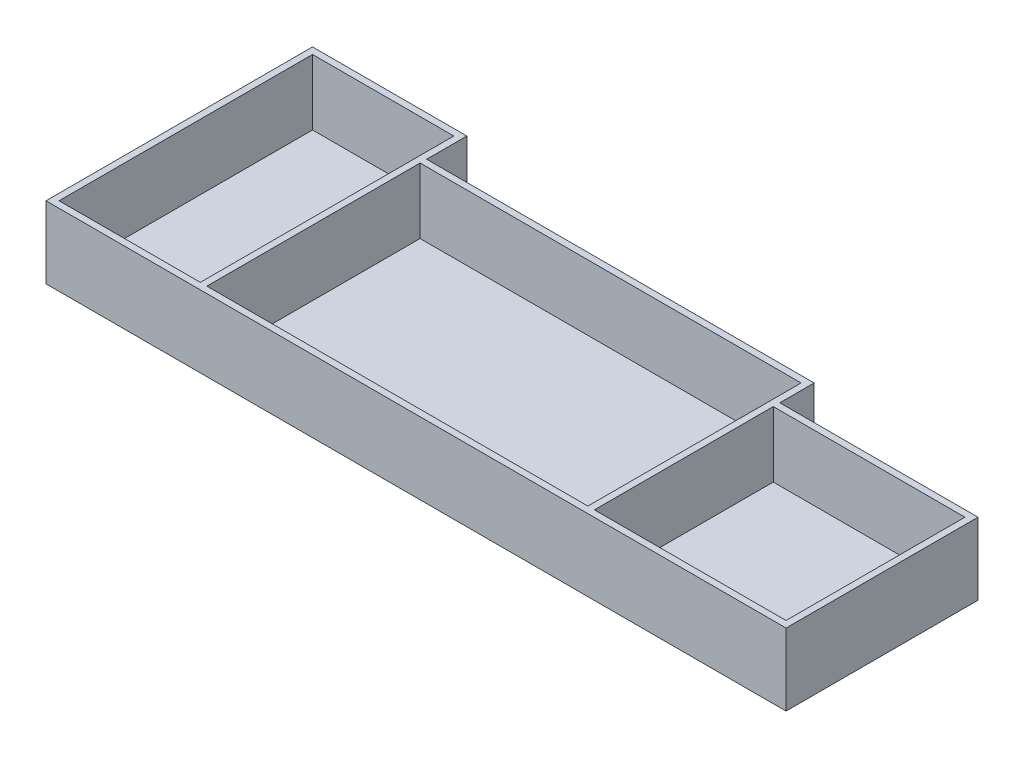
SolidWorks part; units mm, degrees
ref_plane "Front Plane" through (0, 0, 0) normal (0, 0, 1) x (1, 0, 0)
ref_plane "Top Plane" through (0, 0, 0) normal (0, 1, 0) x (1, 0, 0)
ref_plane "Right Plane" through (0, 0, 0) normal (1, 0, 0) x (0, 0, -1)
sketch "Sketch1" plane through (0, 0, 0) normal (0, 1, 0) x (1, 0, 0)
  line L0 (2, 79.5) -> (45.2, 79.5)
  line L1 (0, 0) -> (2, 0)
  line L2 (0, 0) -> (0, 2)
  line L6 (0, 2) -> (0, 79.5)
  line L8 (2, 2) -> (2, 79.5)
  line L10 (0, 79.5) -> (0, 81.5)
  line L11 (0, 81.5) -> (2, 81.5)
  line L13 (2, 2) -> (45.2, 2)
  line L15 (2, 0) -> (44.2, 0)
  line L17 (44.2, 0) -> (46.2, 0)
  line L21 (47.2, 2) -> (163.7, 2)
  line L23 (46.2, 0) -> (162.7, 0)
  line L27 (162.7, 0) -> (164.7, 0)
  line L29 (165.7, 2) -> (224.3, 2)
  line L31 (164.7, 0) -> (224.3, 0)
  line L34 (224.3, 2) -> (224.3, 0)
  line L35 (224.3, 0) -> (226.3, 0)
  line L36 (226.3, -4.0599) -> (226.3, 0)
  line L38 (45.2, 2) -> (45.2, 66.2)
  line L40 (47.2, 2) -> (47.2, 67.2)
  line L44 (45.2, 66.2) -> (45.2, 68.2)
  line L46 (163.7, 2) -> (163.7, 53.7)
  line L48 (165.7, 2) -> (165.7, 56.7)
  line L52 (163.7, 53.7) -> (163.7, 55.7)
  line L53 (45.2, 79.5) -> (45.2, 68.2)
  line L54 (2, 81.5) -> (47.2, 81.5)
  line L55 (47.2, 81.5) -> (47.2, 69.2)
  line L56 (47.2, 69.2) -> (165.7, 69.2)
  line L57 (165.7, 69.2) -> (165.7, 58.7)
  line L58 (47.2, 67.2) -> (163.7, 67.2)
  line L59 (163.7, 67.2) -> (163.7, 55.7)
  line L60 (165.7, 58.7) -> (226.3, 58.7)
  line L61 (226.3, 58.7) -> (226.3, -4.0599)
  line L62 (224.3, 2) -> (224.3, 56.7)
  line L63 (224.3, 56.7) -> (165.7, 56.7)
  dimension "D1" = 77.5
  dimension "D2" = 65.2
  dimension "D3" = 54.7
  dimension "D4" = 43.2
  dimension "D5" = 116.5
  dimension "D6" = 58.6
  dimension "D7" = 2
  dimension "D8" = 2
  dimension "D9" = 2
  dimension "D10" = 2
  dimension "D11" = 2
  dimension "D12" = 2
  dimension "D13" = 2
  dimension "D14" = 2
  dimension "D15" = 2
extrude "Boss-Extrude1" add sketch "Sketch1" against normal blind 2 contours L53 L0 L8 L13 L38 L44 | L62 L63 L48 L29 | L63 L62 L35 L36 L61 L60 L57 L56 L55 L54 L11 L10 L6 L2 L1 L15 L17 L23 L27 L31 L29 L48 L0 L53 L44 L38 L13 L8 L58 L59 L52 L46 L21 L40 | L59 L58 L40 L21 L46 L52 region at (23.6, 0, -40.75) region at (195, 0, -29.35) region at (2.4053, 0, -1) region at (105.45, 0, -34.6)
extrude "Boss-Extrude2" add sketch "Sketch1<4>" along normal blind 20 contours L63 L62 L35 L36 L61 L60 L57 L56 L55 L54 L11 L10 L6 L2 L1 L15 L17 L23 L27 L31 L29 L48 L0 L53 L44 L38 L13 L8 L58 L59 L52 L46 L21 L40 region at (2.4053, 0, -1)
sketch "Sketch1<4>" plane through (0, 0, 0) normal (0, 1, 0) x (1, 0, 0) same geometry as "Sketch1"
